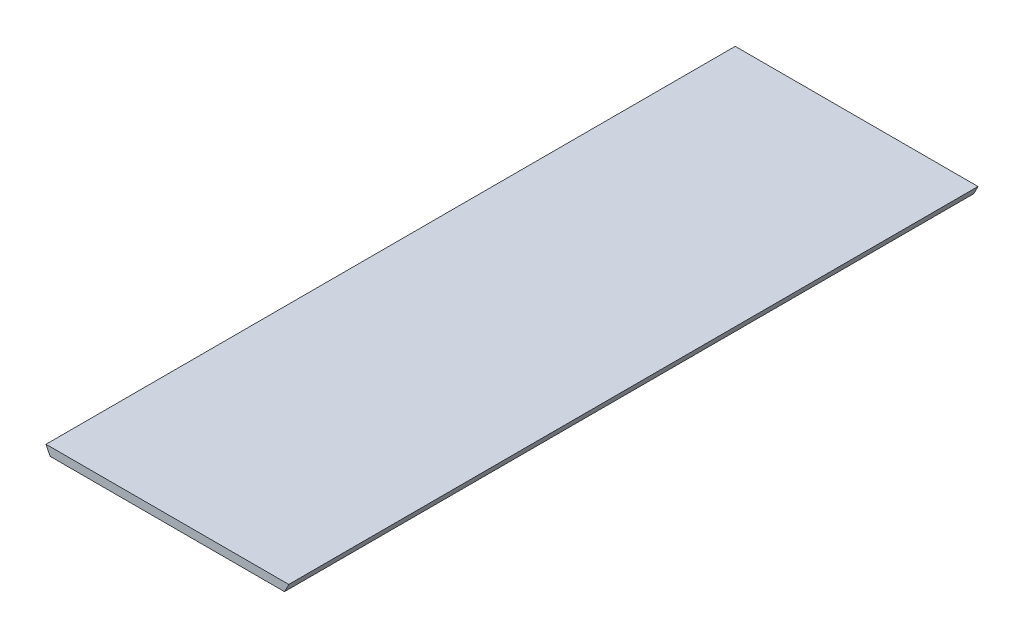
SolidWorks part; units mm, degrees
ref_plane "Front Plane" through (0, 0, 0) normal (0, 0, 1) x (1, 0, 0)
ref_plane "Top Plane" through (0, 0, 0) normal (0, 1, 0) x (1, 0, 0)
ref_plane "Right Plane" through (0, 0, 0) normal (1, 0, 0) x (0, 0, -1)
sketch "Sketch2" plane through (0, 0, 0) normal (0, 0, 1) x (1, 0, 0)
  line L1 (0, -21.393) -> (0, -24.5934) construction
  line L2 (-44.45, -24.5934) -> (44.45, -24.5934)
  line L4 (-46.0758, -21.393) -> (46.0758, -21.393)
  arc A1 (-46.0758, -21.393) -> (-44.45, -24.5934) centre (0, 0) ccw
  arc A3 (44.45, -24.5934) -> (46.0758, -21.393) centre (0, 0) ccw
  dimension "D2" = 3.2004
extrude "Boss-Extrude1" add sketch "Sketch2" along normal blind 261.62 contours L4 A3 L2 A1
